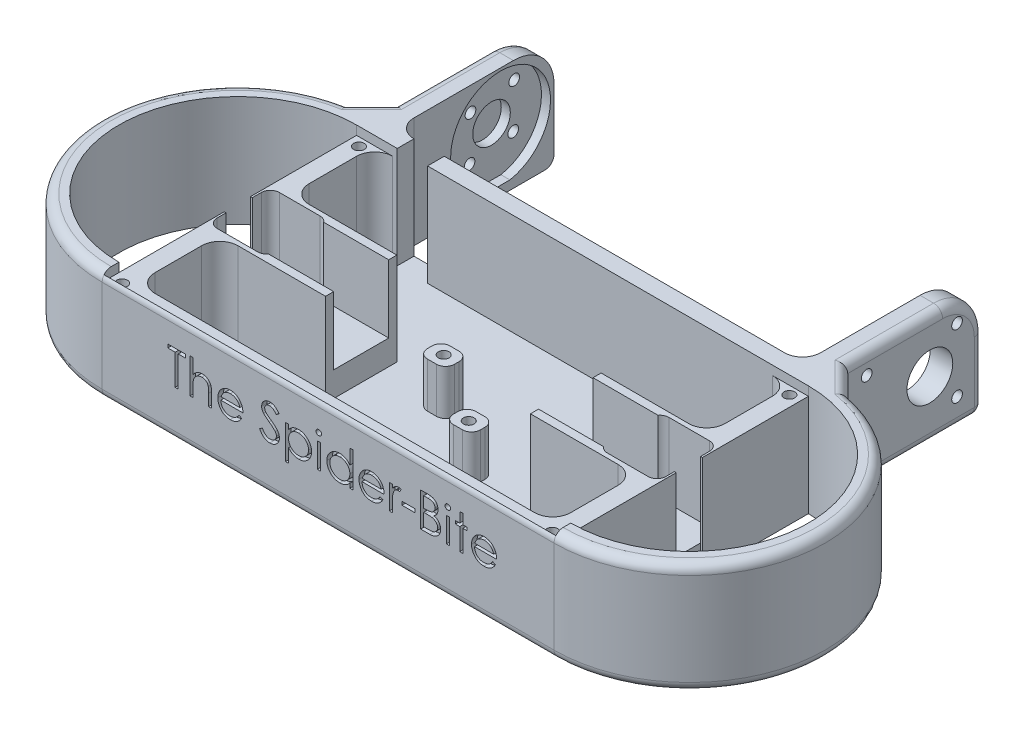
SolidWorks part; units mm, degrees
note: The reader was unsure of these and kept them because the rebuilt part matched: shared geometry of "Sketch2<5>", "Sketch5<3>", "Sketch15<3>".
ref_plane "Front Plane" through (0, 0, 0) normal (0, 0, 1) x (1, 0, 0)
ref_plane "Top Plane" through (0, 0, 0) normal (0, 1, 0) x (1, 0, 0)
ref_plane "Right Plane" through (0, 0, 0) normal (1, 0, 0) x (0, 0, -1)
sketch "Sketch2" plane through (0, 0, 0) normal (0, 1, 0) x (1, 0, 0)
  line L0 (-63.5, 33.401) -> (-58.42, 33.401)
  line L5 (-63.5, 38.1) -> (63.5, 38.1)
  line L6 (-63.5, 38.1) -> (-63.5, -38.1)
  line L7 (-63.5, -38.1) -> (63.5, -38.1)
  line L8 (63.5, 38.1) -> (63.5, -38.1)
  line L14 (-63.5, 7.6454) -> (-63.5, -7.6454)
  line L15 (-46.99, 7.6454) -> (-28.702, 7.6454)
  line L16 (-46.99, -7.8334) -> (-28.702, -7.8334)
  line L19 (-28.702, 7.6454) -> (-46.99, 7.6454)
  line L20 (-28.702, -7.8334) -> (-46.99, -7.8334)
  line L22 (-63.5, 7.0334) -> (-63.5, -9.2226)
  line L27 (-63.5, 9.9314) -> (-63.5, -10.1194)
  line L30 (-46.99, 8.6614) -> (-46.99, 7.6454)
  line L31 (-46.99, 8.6614) -> (-63.5, 8.6614)
  line L32 (-46.99, -8.8494) -> (-63.5, -8.8494)
  line L33 (-63.5, 8.6614) -> (-63.5, -8.8494)
  line L34 (-46.99, -7.8334) -> (-46.99, -8.8494)
  line L35 (-63.5, 9.9314) -> (-63.5, -10.1194)
  line L36 (-63.5, 9.9314) -> (-28.702, 9.9314)
  line L37 (-63.5, -10.1194) -> (-28.702, -10.1194)
  line L39 (-28.702, 9.9314) -> (-28.702, 7.6454)
  line L40 (-28.702, -10.1194) -> (-28.702, -7.8334)
  line L41 (46.99, -7.6454) -> (46.99, -8.6614)
  line L42 (-63.5, 38.1) -> (-57.15, 38.1)
  line L43 (-63.5, 38.1) -> (-63.5, 82.55)
  line L44 (-63.5, 82.55) -> (-57.15, 82.55)
  line L45 (-57.15, 38.1) -> (-57.15, 82.55)
  line L46 (28.702, -9.9314) -> (28.702, -7.6454)
  line L47 (46.99, -7.6454) -> (28.702, -7.6454)
  line L48 (63.5, -9.9314) -> (28.702, -9.9314)
  line L49 (46.99, -8.6614) -> (63.5, -8.6614)
  line L50 (46.99, 8.6614) -> (46.99, 7.6454)
  line L51 (46.99, 8.6614) -> (63.5, 8.6614)
  line L52 (63.5, 9.9314) -> (28.702, 9.9314)
  line L53 (28.702, 9.9314) -> (28.702, 7.6454)
  line L54 (46.99, 7.6454) -> (28.702, 7.6454)
  line L55 (63.5, 82.55) -> (57.15, 82.55)
  line L56 (57.15, 38.1) -> (57.15, 82.55)
  line L57 (63.5, 38.1) -> (57.15, 38.1)
  line L58 (63.5, 38.1) -> (63.5, 82.55)
  line L59 (-63.5, -33.401) -> (-63.5, -38.1)
  line L60 (-63.5, -33.401) -> (63.5, -33.401)
  line L61 (-63.5, -38.1) -> (63.5, -38.1)
  line L62 (63.5, -33.401) -> (63.5, -38.1)
  line L63 (-63.5, 38.1) -> (-63.5, 33.401)
  line L64 (-63.5, 38.1) -> (63.5, 38.1)
  line L65 (-63.5, 33.401) -> (63.5, 33.401)
  line L66 (63.5, 38.1) -> (63.5, 33.401)
  line L67 (-63.5, 8.6614) -> (-62.992, 8.6614)
  line L68 (-63.5, 8.6614) -> (-63.5, 3.5814)
  line L69 (-62.992, 8.6614) -> (-62.992, 3.5814)
  line L70 (-63.5, 3.5814) -> (-62.992, 3.5814)
  line L71 (-63.5, 33.401) -> (-63.5, 9.9314)
  line L72 (-63.5, -3.7694) -> (-62.992, -3.7694)
  line L73 (-62.992, -8.8494) -> (-62.992, -3.7694)
  line L74 (0, 33.401) -> (0, -33.401)
  line L75 (63.5, -3.7694) -> (62.992, -3.7694)
  line L76 (62.992, -8.8494) -> (62.992, -3.7694)
  line L77 (63.5, 3.5814) -> (62.992, 3.5814)
  line L78 (-58.42, 33.401) -> (-58.42, 9.9314)
  line L79 (-63.5, 9.9314) -> (-58.42, 9.9314)
  line L80 (62.992, 8.6614) -> (62.992, 3.5814)
  line L81 (-63.5, 0) -> (63.5, 0)
  line L82 (58.42, 33.401) -> (58.42, 9.9314)
  line L83 (58.42, -33.401) -> (58.42, -9.9314)
  line L84 (-58.42, -33.401) -> (-58.42, -9.9314)
  arc A0 (-63.5, 38.1) -> (-63.5, -38.1) centre (-63.5, 0) ccw
  arc A1 (-63.5, 33.401) -> (-63.5, -33.401) centre (-63.5, 0) ccw
  arc A2 (63.5, 38.1) -> (63.5, -38.1) centre (63.5, 0) cw
  arc A3 (63.5, 33.401) -> (63.5, -33.401) centre (63.5, 0) cw
  point P8 (0, 38.1)
  point P31 (-46.99, 8.6614)
  point P33 (-46.99, -8.8494)
  dimension "D17" = 6.35
  dimension "D1" = 76.2
  dimension "D2" = 127
  dimension "D4" = 44.45
  dimension "D5" = 6.35
  dimension "D6" = 0.508
  dimension "D7" = 15.4788
  dimension "D8" = 34.798
  dimension "D9" = 18.288
  dimension "D10" = 1.016
  dimension "D11" = 1.016
  dimension "D12" = 1.27
  dimension "D13" = 1.27
  dimension "D14" = 5.08
  dimension "D15" = 5.08
  dimension "D16" = 5.08
  dimension "D3" = 4.699
extrude "Boss-Extrude1" add sketch "Sketch2" along normal blind 28.575
extrude "Boss-Extrude5" add sketch "Sketch2<5>" against normal blind 2.54 separate body
sketch "Sketch2<5>" plane through (0, 0, 0) normal (0, 1, 0) x (1, 0, 0) same geometry as "Sketch2"
sketch "Sketch5" plane through (-57.15, 0, 0) normal (1, 0, 0) x (0, 0, -1)
  line L0 (38.1, 28.575) -> (82.55, 28.575) construction
  circle A0 centre (67.521, 13.784) radius 14.0335
  circle A1 centre (67.521, 13.784) radius 5.2787
  point P2 (60.325, 28.575)
  line M3 (38.1, 0) -> (82.55, 0)
  dimension "D1" = 28.067
fillet "Fillet1" radius 11.43 2 edges at (60.325, 28.575, -82.55) (-60.325, 28.575, -82.55)
chamfer "Chamfer4" distance 6.35 angle 45 2 edges at (63.5, 14.2875, -38.1) (-63.5, 14.2875, -38.1)
chamfer "Chamfer5" distance 6.35 angle 45 2 edges at (63.5, -1.27, -38.1) (-63.5, -1.27, -38.1)
fillet "Fillet2" radius 5.08 10 edges at (58.42, 14.2875, 33.401) (-58.42, 14.2875, 33.401) (-58.42, 14.2875, -33.401) (58.42, 14.2875, -33.401) (57.15, 14.2875, -38.1) (-57.15, 14.2875, -38.1) (-58.42, 14.2875, 10.1194) (-58.42, 14.2875, -9.9314) (58.42, 14.2875, -9.9314) (58.42, 14.2875, 9.9314)
extrude "Cut-Extrude1" cut sketch "Sketch5" against normal blind 2.54 contours A1 | A0 A1 M3
fillet "Fillet3" radius 5.08 2 edges at (-57.15, -1.27, -38.1) (57.15, -1.27, -38.1)
fillet "Fillet4" radius 2.54 8 edges at (46.99, 14.2875, 8.6614) (46.99, 14.2875, -8.6614) (-46.99, 14.2875, 8.8494) (-46.99, 14.2875, -8.6614) (62.992, 14.2875, 8.6614) (62.992, 14.2875, -8.6614) (-62.992, 14.2875, 8.8494) (-62.992, 14.2875, -8.6614)
sketch "Sketch8" plane through (0, 0, -38.1) normal (0, 0, -1) x (-1, 0, 0)
  line L4 (43.5503, -3.8224) -> (43.5503, 28.575)
  line L5 (52.07, 28.575) -> (-52.07, 28.575) construction
  line L6 (43.5503, -3.8224) -> (56.6206, -3.8224)
  line L11 (56.6206, -3.8224) -> (56.2503, 28.575)
  line L13 (56.2503, 28.575) -> (43.5503, 28.575)
  dimension "D1" = 12.7
extrude "Cut-Extrude3" cut sketch "Sketch8" against normal up to surface (4.699 mm away)
sketch "Sketch11" plane through (-59.69, 0, 0) normal (1, 0, 0) x (0, 0, -1)
  circle A0 centre (73.8946, 21.2097) radius 1.5
  circle A1 centre (61.6138, 19.3573) radius 1.5
  circle A2 centre (73.6301, 8.7928) radius 1.5
  circle A3 centre (61.3492, 6.9404) radius 1.5
  dimension "D1" = 3
  dimension "D2" = 12.2808
  dimension "D3" = 12.4169
extrude "Cut-Extrude4" cut sketch "Sketch11" against normal through all
sketch "Sketch14" plane through (0, 0, 0) normal (0, 1, 0) x (1, 0, 0)
  line L0 (-14.9865, 8.6196) -> (12.2355, 8.6196)
  line L1 (-14.9865, 8.6196) -> (-14.9865, -10.0436)
  line L2 (12.2355, 8.6196) -> (12.2355, -10.0436)
  line L3 (-14.9865, -10.0436) -> (12.2355, -10.0436)
  line L5 (-14.9865, 8.6196) -> (-7.3665, 8.6196)
  line L6 (-14.9865, 8.6196) -> (-14.9865, 2.2696)
  line L7 (-14.9865, 2.2696) -> (-7.3665, 2.2696)
  line L8 (-7.3665, 8.6196) -> (-7.3665, 2.2696)
  line L9 (12.2355, -10.0436) -> (4.6155, -10.0436)
  line L10 (12.2355, -10.0436) -> (12.2355, -3.6936)
  line L11 (12.2355, -3.6936) -> (4.6155, -3.6936)
  line L12 (4.6155, -10.0436) -> (4.6155, -3.6936)
  circle A0 centre (-11.1765, 5.5716) radius 1.5
  circle A1 centre (8.4255, -6.9956) radius 1.5
  dimension "D1" = 3
  dimension "D2" = 3
  dimension "D3" = 3.048
  dimension "D4" = 3.81
  dimension "D5" = 3.81
  dimension "D6" = 3.048
  dimension "D7" = 7.62
  dimension "D8" = 6.35
  dimension "D9" = 7.62
  dimension "D10" = 6.35
extrude "Boss-Extrude11" add sketch "Sketch14" along normal blind 12.7 contours L8 L0 L1 L7 A0 | L12 L3 L2 L11 A1
fillet "Fillet6" radius 2.54 8 edges at (-14.9865, 6.35, -8.6196) (-7.3665, 6.35, -2.2696) (-7.3665, 6.35, -8.6196) (12.2355, 6.35, 3.6936) (4.6155, 6.35, 3.6936) (4.6155, 6.35, 10.0436) (12.2355, 6.35, 10.0436) (-14.9865, 6.35, -2.2696)
sketch "Sketch15" plane through (0, 28.575, 0) normal (0, 1, 0) x (1, 0, 0)
  line L0 (-63.5, 33.401) -> (63.5, 33.401)
  line L1 (-63.5, 33.401) -> (-63.5, -37.5697)
  line L2 (63.5, 33.401) -> (63.5, -37.5697)
  line L3 (-63.5, -37.5697) -> (63.5, -37.5697)
  line L4 (0, 33.401) -> (0, -37.5697)
  line L5 (-63.5, -2.0843) -> (63.5, -2.0843)
  circle A4 centre (-60.4829, 31.0599) radius 1.5
  circle A5 centre (60.4829, 31.0599) radius 1.5
  circle A6 centre (60.452, -35.5377) radius 1.5
  circle A7 centre (-60.452, -35.5377) radius 1.5
  dimension "D1" = 3.048
  dimension "D3" = 2.032
  dimension "D2" = 3.048
extrude "Cut-Extrude6" cut sketch "Sketch15" against normal blind 2.54 contours L5 L1 L3 L4 A7 | L1 L5 L4 L0 A4 | L4 L5 L2 L0 A5 | L5 L4 L3 L2 A6 | A4 | A5 | A6 | A7
sketch "Sketch27" plane through (0, 0, 0) normal (0, 1, 0) x (1, 0, 0)
  line L0 (0, 38.1) -> (0, 64.8828)
  line L1 (-43.5503, 38.1) -> (52.07, 38.1) construction
  line L2 (-28.702, 7.6454) -> (-28.702, -7.8334)
  line L3 (-28.702, 7.6454) -> (-47.2876, 7.6454)
  line L4 (-28.702, -7.8334) -> (-47.2876, -7.8334)
  line L5 (-47.2876, 7.6454) -> (-47.2876, -7.8334)
  line L6 (28.702, -7.8334) -> (47.2876, -7.8334)
  line L7 (28.702, 7.6454) -> (28.702, -7.8334)
  line L8 (28.702, 7.6454) -> (47.2876, 7.6454)
  line L9 (47.2876, 7.6454) -> (47.2876, -7.8334)
extrude "Boss-Extrude12" add sketch "Sketch27" along normal blind 6.985 contours L3 L5 L4 L2 | L9 L8 L7 L6
extrude "Cut-Extrude9" cut sketch "Sketch5<3>" against normal blind 5.08 contours A1
sketch "Sketch5<3>" plane through (-57.15, 0, 0) normal (1, 0, 0) x (0, 0, -1) same geometry as "Sketch5"
sketch "Sketch16" plane through (57.15, 0, 0) normal (-1, 0, 0) x (0, 0, 1)
  line L0 (-43.18, 28.575) -> (-71.12, 28.575) construction
  circle A0 centre (-67.521, 13.784) radius 6.4389
  circle A1 centre (-67.521, 13.784) radius 6.8072
  circle A2 centre (-67.521, 13.784) radius 5.2787 construction
  point P2 (-57.15, 28.575)
  dimension "D1" = 12.8778
extrude "Cut-Extrude7" cut sketch "Sketch16" against normal through all contours A0
extrude "Cut-Extrude10" cut sketch "Sketch15<3>" against normal blind 8.89 contours A4 | A7 | A6 | A5
sketch "Sketch15<3>" plane through (0, 28.575, 0) normal (0, 1, 0) x (1, 0, 0) same geometry as "Sketch15"
sketch "Sketch17" plane through (0, 0, 38.1) normal (0, 0, 1) x (1, 0, 0)
  text T0 "The Spider-Bite " font "Century Gothic" height in points 36
extrude "Cut-Extrude11" cut sketch "Sketch17" against normal blind 1.524
sketch "Sketch26" plane through (63.5, 0, 0) normal (1, 0, 0) x (0, 0, -1)
  line L20 (82.55, -2.54) -> (82.55, 17.145) construction
  circle A0 centre (49.7689, 22.9274) radius 1.5
  circle A1 centre (75.1689, 22.9274) radius 1.5
  circle A2 centre (49.7689, 5.08) radius 1.5
  circle A3 centre (75.1689, 5.08) radius 1.5
  dimension "D1" = 3
  dimension "D2" = 3
  dimension "D3" = 3
  dimension "D4" = 3
  dimension "D8" = 25.4
  dimension "D9" = 7.3811
extrude "Cut-Extrude20" cut sketch "Sketch26" against normal up to surface (6.35 mm away) contours A0 | A1 | A3 | A2 up to face at (57.15, 13.784, -61.0821)
fillet "Fillet7" radius 2.54 2 edges at (60.325, -2.54, -82.55) (-60.325, -2.54, -82.55)
fillet "Fillet8" radius 2.54 20 edges at (-101.4376, 28.575, 3.5141) (-101.4376, -2.54, 3.5141) (0, 28.575, 38.1) (0, -2.54, 38.1) (101.4376, 28.575, 3.5141) (-66.9991, -2.54, -40.9509) (-66.9991, 28.575, -40.9509) (66.9991, -2.54, -40.9509) (66.9991, 28.575, -40.9509) (101.4376, -2.54, 3.5141) (63.5, -2.54, -62.23) (63.5, -1.7961, -81.8061) (63.5, 8.5725, -82.55) (63.5, 25.2272, -79.2022) (-63.5, -2.54, -62.23) (-63.5, -1.7961, -81.8061) (-63.5, 8.5725, -82.55) (-63.5, 25.2272, -79.2022) (63.5, 28.575, -57.785) (-63.5, 28.575, -57.785)
sketch "Sketch28" plane through (0, 0, 0) normal (0, 1, 0) x (1, 0, 0)
  line L0 (-62.992, 3.5814) -> (-62.992, -3.7694)
  line L1 (62.992, 3.5814) -> (62.992, -3.7694)
  line L10 (-47.2876, -7.8334) -> (-47.2876, 7.6454)
  line L11 (-47.2876, 7.6454) -> (-46.99, 7.6454)
  line L12 (-49.022, 8.6614) -> (-60.452, 8.6614)
  line L13 (-62.992, 6.1214) -> (-62.992, 3.5814)
  line L14 (-62.992, 3.5814) -> (-63.5, 3.5814)
  line L15 (-63.5, 3.5814) -> (-63.5, -3.7694)
  line L16 (-63.5, -3.7694) -> (-62.992, -3.7694)
  line L17 (-62.992, -3.7694) -> (-62.992, -6.3094)
  line L18 (-60.452, -8.8494) -> (-49.022, -8.8494)
  line L19 (-46.99, -7.8334) -> (-47.2876, -7.8334)
  line L20 (-47.2876, -7.8334) -> (-47.2876, 7.6454)
  line L21 (-47.2876, 7.6454) -> (-46.99, 7.6454)
  line L22 (-49.022, 8.6614) -> (-60.452, 8.6614)
  line L23 (-62.992, 6.1214) -> (-62.992, 3.5814)
  line L27 (-62.992, -3.7694) -> (-62.992, -6.3094)
  line L28 (-60.452, -8.8494) -> (-49.022, -8.8494)
  line L29 (-46.99, -7.8334) -> (-47.2876, -7.8334)
  line L30 (46.99, 7.6454) -> (47.2876, 7.6454)
  line L31 (47.2876, 7.6454) -> (47.2876, -7.8334)
  line L32 (47.2876, -7.8334) -> (47.1456, -7.8334)
  line L33 (49.022, -8.6614) -> (60.452, -8.6614)
  line L34 (62.992, -6.1214) -> (62.992, -3.7694)
  line L35 (62.992, -3.7694) -> (63.5, -3.7694)
  line L36 (63.5, -3.7694) -> (63.5, 3.5814)
  line L37 (63.5, 3.5814) -> (62.992, 3.5814)
  line L38 (62.992, 3.5814) -> (62.992, 6.1214)
  line L39 (60.452, 8.6614) -> (49.022, 8.6614)
  line L40 (46.99, 7.6454) -> (47.2876, 7.6454)
  line L41 (47.2876, 7.6454) -> (47.2876, -7.8334)
  line L42 (47.2876, -7.8334) -> (47.1456, -7.8334)
  line L43 (49.022, -8.6614) -> (60.452, -8.6614)
  line L44 (62.992, -6.1214) -> (62.992, -3.7694)
  line L48 (62.992, 3.5814) -> (62.992, 6.1214)
  line L49 (60.452, 8.6614) -> (49.022, 8.6614)
  arc A4 (-46.99, 7.6454) -> (-49.022, 8.6614) centre (-49.022, 6.1214) ccw
  arc A5 (-60.452, 8.6614) -> (-62.992, 6.1214) centre (-60.452, 6.1214) ccw
  arc A6 (-62.992, -6.3094) -> (-60.452, -8.8494) centre (-60.452, -6.3094) ccw
  arc A7 (-49.022, -8.8494) -> (-46.99, -7.8334) centre (-49.022, -6.3094) ccw
  arc A8 (-46.99, 7.6454) -> (-49.022, 8.6614) centre (-49.022, 6.1214) ccw
  arc A9 (-60.452, 8.6614) -> (-62.992, 6.1214) centre (-60.452, 6.1214) ccw
  arc A10 (-62.992, -6.3094) -> (-60.452, -8.8494) centre (-60.452, -6.3094) ccw
  arc A11 (-49.022, -8.8494) -> (-46.99, -7.8334) centre (-49.022, -6.3094) ccw
  arc A12 (47.1456, -7.8334) -> (49.022, -8.6614) centre (49.022, -6.1214) ccw
  arc A13 (60.452, -8.6614) -> (62.992, -6.1214) centre (60.452, -6.1214) ccw
  arc A14 (62.992, 6.1214) -> (60.452, 8.6614) centre (60.452, 6.1214) ccw
  arc A15 (49.022, 8.6614) -> (46.99, 7.6454) centre (49.022, 6.1214) ccw
  arc A16 (47.1456, -7.8334) -> (49.022, -8.6614) centre (49.022, -6.1214) ccw
  arc A17 (60.452, -8.6614) -> (62.992, -6.1214) centre (60.452, -6.1214) ccw
  arc A18 (62.992, 6.1214) -> (60.452, 8.6614) centre (60.452, 6.1214) ccw
  arc A19 (49.022, 8.6614) -> (46.99, 7.6454) centre (49.022, 6.1214) ccw
  dimension "D1" = 0
  dimension "D2" = 0
extrude "Boss-Extrude13" add sketch "Sketch28" along normal up to vertex (4.985 mm away)
